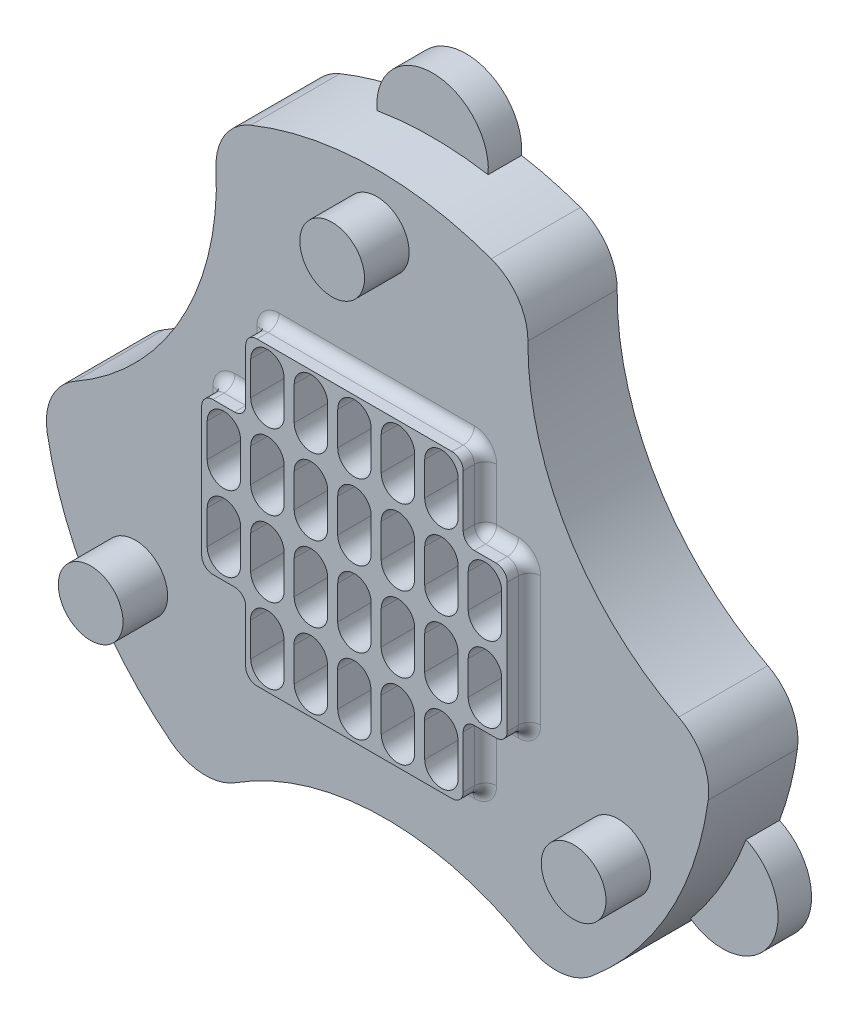
SolidWorks part; units mm, degrees
ref_plane "Спереди" through (0, 0, 0) normal (0, 0, 1) x (1, 0, 0)
ref_plane "Сверху" through (0, 0, 0) normal (0, 1, 0) x (1, 0, 0)
ref_plane "Справа" through (0, 0, 0) normal (1, 0, 0) x (0, 0, -1)
sketch "Sketch1" plane through (0, 0, 0) normal (0, 0, 1) x (1, 0, 0)
  line L0 (3.9, 6.755) -> (7.8, 0) construction
  line L2 (5.85, 10.1325) -> (11.7, 0) construction
  line L4 (7.8, 13.51) -> (15.6, 0) construction
  circle A61 centre (0, 0) radius 20
  circle A131 centre (0, 0) radius 1.25
  circle A484 centre (3.9, 0) radius 1.25
  circle A485 centre (7.8, 0) radius 1.25
  circle A486 centre (11.7, 0) radius 1.25
  circle A487 centre (15.6, 0) radius 1.25
  circle A488 centre (1.95, -3.3775) radius 1.25
  circle A489 centre (3.9, -6.755) radius 1.25
  circle A490 centre (5.85, -10.1325) radius 1.25
  circle A491 centre (7.8, -13.51) radius 1.25
  circle A492 centre (-1.95, -3.3775) radius 1.25
  circle A493 centre (-3.9, -6.755) radius 1.25
  circle A494 centre (-5.85, -10.1325) radius 1.25
  circle A495 centre (-7.8, -13.51) radius 1.25
  circle A496 centre (-3.9, 0) radius 1.25
  circle A497 centre (-7.8, 0) radius 1.25
  circle A498 centre (-11.7, 0) radius 1.25
  circle A499 centre (-15.6, 0) radius 1.25
  circle A500 centre (-1.95, 3.3775) radius 1.25
  circle A501 centre (-3.9, 6.755) radius 1.25
  circle A502 centre (-5.85, 10.1325) radius 1.25
  circle A503 centre (-7.8, 13.51) radius 1.25
  circle A504 centre (1.95, 3.3775) radius 1.25
  circle A505 centre (3.9, 6.755) radius 1.25
  circle A506 centre (5.85, 10.1325) radius 1.25
  circle A507 centre (7.8, 13.51) radius 1.25
  circle A508 centre (5.85, 3.3775) radius 1.25
  circle A509 centre (7.8, 6.755) radius 1.25
  circle A510 centre (9.75, 3.3775) radius 1.25
  circle A511 centre (11.7, 6.755) radius 1.25
  circle A512 centre (9.7491, 10.1341) radius 1.25
  circle A513 centre (13.6509, 3.3759) radius 1.25
  circle A514 centre (5.85, -3.3791) radius 1.25
  circle A515 centre (9.75, -3.3791) radius 1.25
  circle A516 centre (7.8, -6.7566) radius 1.25
  circle A517 centre (11.7, -6.7566) radius 1.25
  circle A518 centre (9.7491, -10.1356) radius 1.25
  circle A519 centre (13.6509, -3.3775) radius 1.25
  circle A520 centre (-0.0013, -6.7573) radius 1.25
  circle A521 centre (1.9487, -10.1348) radius 1.25
  circle A522 centre (-1.9513, -10.1348) radius 1.25
  circle A523 centre (-0.0013, -13.5123) radius 1.25
  circle A524 centre (-3.9032, -13.5123) radius 1.25
  circle A525 centre (3.9005, -13.5123) radius 1.25
  circle A526 centre (-5.8527, -3.3791) radius 1.25
  circle A527 centre (-7.8027, -6.7566) radius 1.25
  circle A528 centre (-9.7527, -3.3791) radius 1.25
  circle A529 centre (-11.7027, -6.7566) radius 1.25
  circle A530 centre (-13.6536, -3.3775) radius 1.25
  circle A531 centre (-9.7518, -10.1356) radius 1.25
  circle A532 centre (-5.8527, 3.3775) radius 1.25
  circle A533 centre (-9.7527, 3.3775) radius 1.25
  circle A534 centre (-7.8027, 6.755) radius 1.25
  circle A535 centre (-11.7027, 6.755) radius 1.25
  circle A536 centre (-9.7518, 10.1341) radius 1.25
  circle A537 centre (-13.6536, 3.3759) radius 1.25
  circle A538 centre (-0.0014, 6.7558) radius 1.25
  circle A539 centre (-1.9514, 10.1333) radius 1.25
  circle A540 centre (1.9486, 10.1333) radius 1.25
  circle A541 centre (-0.0014, 13.5108) radius 1.25
  circle A542 centre (3.9005, 13.5108) radius 1.25
  circle A543 centre (-3.9032, 13.5108) radius 1.25
  circle A544 centre (13.65, -1.1258) radius 2.2517 construction
  circle A545 centre (11.7009, -4.5044) radius 2.2522 construction
  circle A546 centre (9.75, -7.8834) radius 2.2522 construction
  circle A547 centre (7.7987, -11.2591) radius 2.2509 construction
  circle A548 centre (13.65, -1.1258) radius 0.65
  circle A549 centre (11.7009, -4.5044) radius 0.65
  circle A550 centre (9.75, -7.8834) radius 0.65
  circle A551 centre (7.7987, -11.2591) radius 0.65
  circle A552 centre (9.75, -1.1258) radius 0.65
  circle A553 centre (7.8009, -4.5044) radius 0.65
  circle A554 centre (5.85, -7.8834) radius 0.65
  circle A555 centre (3.8987, -11.2591) radius 0.65
  circle A556 centre (5.85, -1.1258) radius 0.65
  circle A557 centre (3.9009, -4.5044) radius 0.65
  circle A558 centre (1.95, -7.8834) radius 0.65
  circle A559 centre (-0.0013, -11.2591) radius 0.65
  circle A560 centre (1.95, -1.1258) radius 0.65
  circle A561 centre (0.0009, -4.5044) radius 0.65
  circle A562 centre (-1.95, -7.8834) radius 0.65
  circle A563 centre (-3.9013, -11.2591) radius 0.65
  circle A564 centre (-1.95, -1.1258) radius 0.65
  circle A565 centre (-3.8991, -4.5044) radius 0.65
  circle A566 centre (-5.85, -7.8834) radius 0.65
  circle A567 centre (-7.8013, -11.2591) radius 0.65
  circle A568 centre (-5.85, -1.1258) radius 0.65
  circle A569 centre (-7.7991, -4.5044) radius 0.65
  circle A570 centre (-9.75, -7.8834) radius 0.65
  circle A572 centre (-9.75, -1.1258) radius 0.65
  circle A573 centre (-11.6991, -4.5044) radius 0.65
  circle A576 centre (-13.65, -1.1258) radius 0.65
  circle A587 centre (0, 2.2517) radius 2.2517 construction
  circle A588 centre (0, 2.2517) radius 0.65
  circle A589 centre (3.9, 2.2517) radius 0.65
  circle A590 centre (7.8, 2.2517) radius 0.65
  circle A591 centre (11.7, 2.2517) radius 0.65
  circle A592 centre (15.6, 2.2517) radius 0.65
  circle A593 centre (1.9491, 5.6297) radius 2.2522 construction
  circle A594 centre (1.9491, 5.6297) radius 0.65
  circle A595 centre (5.8491, 5.6297) radius 0.65
  circle A596 centre (9.7491, 5.6297) radius 0.65
  circle A597 centre (13.6491, 5.6297) radius 0.65
  circle A598 centre (3.8991, 9.0072) radius 2.2522 construction
  circle A599 centre (3.8991, 9.0072) radius 0.65
  circle A600 centre (7.7991, 9.0072) radius 0.65
  circle A601 centre (11.6991, 9.0072) radius 0.65
  circle A602 centre (5.85, 12.3842) radius 2.2517 construction
  circle A603 centre (5.85, 12.3842) radius 0.65
  circle A604 centre (9.75, 12.3842) radius 0.65
  circle A605 centre (5.85, -14.6358) radius 0.65
  circle A606 centre (1.9509, -14.6353) radius 0.65
  circle A607 centre (-1.9491, -14.6353) radius 0.65
  circle A608 centre (-5.85, -14.6358) radius 0.65
  circle A609 centre (-15.6, 2.2517) radius 0.65
  circle A610 centre (-13.65, 5.6281) radius 0.65
  circle A611 centre (-11.7, 9.0056) radius 0.65
  circle A612 centre (-9.75, 12.3842) radius 0.65
  circle A613 centre (-5.85, 12.3842) radius 0.65
  circle A614 centre (-1.95, 12.3842) radius 0.65
  circle A615 centre (1.95, 12.3842) radius 0.65
  circle A616 centre (-7.8, 9.0056) radius 0.65
  circle A617 centre (-9.75, 5.6281) radius 0.65
  circle A618 centre (-11.7, 2.2517) radius 0.65
  circle A619 centre (-3.9, 9.0056) radius 0.65
  circle A620 centre (-5.85, 5.6281) radius 0.65
  circle A621 centre (-7.8, 2.2517) radius 0.65
  circle A622 centre (0, 9.0056) radius 0.65
  circle A623 centre (-1.95, 5.6281) radius 0.65
  circle A624 centre (-3.9, 2.2517) radius 0.65
  circle A625 centre (-15.5991, -4.5044) radius 0.65
  circle A626 centre (-13.65, -7.8834) radius 0.65
  circle A627 centre (-17.55, -7.8834) radius 0.65
  circle A628 centre (-19.5013, -11.2591) radius 0.65
  circle A629 centre (-15.6013, -11.2591) radius 0.65
  circle A630 centre (-11.7013, -11.2591) radius 0.65
  point P51 (0, 0)
  point P125 (-0.0013, -0.0008)
  point P231 (0, 0)
  dimension "D1" = 5
  dimension "D3" = 6
  dimension "D5" = 8
  dimension "D7" = 4
  dimension "D11" = 4
  dimension "D2" = 6
  dimension "D6" = 5
  dimension "D8" = 3
  dimension "D9" = 2
  dimension "D4" = 1.3
  dimension "D10" = 3
ref_plane "Plane1" through (0, 0, 10) normal (0, 0, 1) x (1, 0, 0)
sketch "Sketch2" plane through (0, 0, 10) normal (0, 0, 1) x (1, 0, 0)
  line L0 (-7.8, 13.51) -> (-7.8027, 6.755) construction
  line L1 (-9.7518, 10.1341) -> (-5.85, 10.1325) construction
  line L2 (-7.8008, 11.6325) -> (-7.8019, 8.6325) construction
  line L3 (-6.3008, 11.6319) -> (-6.3019, 8.6319)
  line L4 (-9.3008, 11.6331) -> (-9.3019, 8.6331)
  line L5 (-5.4008, 11.6331) -> (-5.4019, 8.6331)
  line L6 (-2.4008, 11.6319) -> (-2.4019, 8.6319)
  line L7 (-3.9008, 11.6325) -> (-3.9019, 8.6325) construction
  line L8 (-1.5008, 11.6331) -> (-1.5019, 8.6331)
  line L9 (1.4992, 11.6319) -> (1.4981, 8.6319)
  line L10 (-0.0008, 11.6325) -> (-0.0019, 8.6325) construction
  line L11 (2.3992, 11.6331) -> (2.3981, 8.6331)
  line L12 (5.3992, 11.6319) -> (5.3981, 8.6319)
  line L13 (3.8992, 11.6325) -> (3.8981, 8.6325) construction
  line L14 (6.2992, 11.6331) -> (6.2981, 8.6331)
  line L15 (9.2992, 11.6319) -> (9.2981, 8.6319)
  line L16 (7.7992, 11.6325) -> (7.7981, 8.6325) construction
  line L17 (-9.7518, 10.1341) -> (-9.7527, 3.3775) construction
  line L18 (-11.7027, 6.755) -> (-7.8027, 6.755) construction
  line L19 (-10.2035, 1.8767) -> (-10.202, 4.8767)
  line L22 (-9.7527, 3.3775) -> (-5.8527, 3.3775) construction
  line L25 (-7.8027, 6.755) -> (-7.8, 0) construction
  line L26 (-7.8035, 1.8775) -> (-7.8019, 4.8775) construction
  line L27 (-9.3035, 1.8782) -> (-9.3019, 4.8782)
  line L28 (-6.3035, 1.8767) -> (-6.3019, 4.8767)
  line L29 (-2.4035, 1.8767) -> (-2.4019, 4.8767)
  line L30 (-5.4035, 1.8782) -> (-5.4019, 4.8782)
  line L31 (-3.9035, 1.8775) -> (-3.9019, 4.8775) construction
  line L32 (1.4965, 1.8767) -> (1.4981, 4.8767)
  line L33 (-1.5035, 1.8782) -> (-1.5019, 4.8782)
  line L34 (-0.0035, 1.8775) -> (-0.0019, 4.8775) construction
  line L35 (5.3965, 1.8767) -> (5.3981, 4.8767)
  line L36 (2.3965, 1.8782) -> (2.3981, 4.8782)
  line L37 (3.8965, 1.8775) -> (3.8981, 4.8775) construction
  line L38 (9.2965, 1.8767) -> (9.2981, 4.8767)
  line L39 (6.2965, 1.8782) -> (6.2981, 4.8782)
  line L40 (7.7965, 1.8775) -> (7.7981, 4.8775) construction
  line L41 (13.1965, 1.8767) -> (13.1981, 4.8767)
  line L42 (10.1965, 1.8782) -> (10.1981, 4.8782)
  line L43 (11.6965, 1.8775) -> (11.6981, 4.8775) construction
  line L44 (-13.2035, 1.8782) -> (-13.2019, 4.8782)
  line L45 (-11.7035, 1.8775) -> (-11.702, 4.8775) construction
  line L46 (-9.7527, -3.3791) -> (-5.8527, -3.3791) construction
  line L47 (-7.8, 0) -> (-7.8027, -6.7566) construction
  line L48 (-7.8046, -4.8791) -> (-7.8008, -1.8791) construction
  line L49 (-9.3046, -4.8771) -> (-9.3007, -1.8771)
  line L50 (-6.3047, -4.881) -> (-6.3008, -1.881)
  line L51 (-2.4047, -4.881) -> (-2.4008, -1.881)
  line L52 (-5.4046, -4.8771) -> (-5.4007, -1.8771)
  line L53 (-3.9046, -4.8791) -> (-3.9008, -1.8791) construction
  line L54 (1.4953, -4.881) -> (1.4992, -1.881)
  line L55 (-1.5046, -4.8771) -> (-1.5007, -1.8771)
  line L56 (-0.0046, -4.8791) -> (-0.0008, -1.8791) construction
  line L57 (5.3953, -4.881) -> (5.3992, -1.881)
  line L58 (2.3954, -4.8771) -> (2.3993, -1.8771)
  line L59 (3.8954, -4.8791) -> (3.8992, -1.8791) construction
  line L60 (9.2953, -4.881) -> (9.2992, -1.881)
  line L61 (6.2954, -4.8771) -> (6.2993, -1.8771)
  line L62 (7.7954, -4.8791) -> (7.7992, -1.8791) construction
  line L63 (13.1953, -4.881) -> (13.1992, -1.881)
  line L64 (10.1954, -4.8771) -> (10.1993, -1.8771)
  line L65 (11.6954, -4.8791) -> (11.6992, -1.8791) construction
  line L66 (-10.2047, -4.881) -> (-10.2008, -1.881)
  line L67 (-13.2046, -4.8771) -> (-13.2007, -1.8771)
  line L68 (-11.7046, -4.8791) -> (-11.7008, -1.8791) construction
  line L69 (-9.7518, -10.1356) -> (-5.482, -10.1356) construction
  line L70 (-7.8027, -6.7566) -> (-7.8, -13.51) construction
  line L71 (-7.8259, -8.6356) -> (-7.8007, -11.6356) construction
  line L72 (-6.3259, -8.623) -> (-6.3008, -11.623)
  line L73 (-9.3258, -8.6482) -> (-9.3007, -11.6482)
  line L74 (-5.4258, -8.6482) -> (-5.4007, -11.6482)
  line L75 (-2.4259, -8.623) -> (-2.4008, -11.623)
  line L76 (-3.9259, -8.6356) -> (-3.9007, -11.6356) construction
  line L77 (-1.5258, -8.6482) -> (-1.5007, -11.6482)
  line L78 (1.4741, -8.623) -> (1.4992, -11.623)
  line L79 (-0.0259, -8.6356) -> (-0.0007, -11.6356) construction
  line L80 (2.3742, -8.6482) -> (2.3993, -11.6482)
  line L81 (5.3741, -8.623) -> (5.3992, -11.623)
  line L82 (3.8741, -8.6356) -> (3.8993, -11.6356) construction
  line L83 (6.2742, -8.6482) -> (6.2993, -11.6482)
  line L84 (9.2741, -8.623) -> (9.2992, -11.623)
  line L85 (7.7741, -8.6356) -> (7.7993, -11.6356) construction
  arc A0 (-6.3008, 11.6319) -> (-9.3008, 11.6331) centre (-7.8008, 11.6325) ccw
  arc A1 (-9.3019, 8.6331) -> (-6.3019, 8.6319) centre (-7.8019, 8.6325) ccw
  arc A2 (-2.4008, 11.6319) -> (-5.4008, 11.6331) centre (-3.9008, 11.6325) ccw
  arc A3 (-5.4019, 8.6331) -> (-2.4019, 8.6319) centre (-3.9019, 8.6325) ccw
  arc A4 (1.4992, 11.6319) -> (-1.5008, 11.6331) centre (-0.0008, 11.6325) ccw
  arc A5 (-1.5019, 8.6331) -> (1.4981, 8.6319) centre (-0.0019, 8.6325) ccw
  arc A6 (5.3992, 11.6319) -> (2.3992, 11.6331) centre (3.8992, 11.6325) ccw
  arc A7 (2.3981, 8.6331) -> (5.3981, 8.6319) centre (3.8981, 8.6325) ccw
  arc A8 (9.2992, 11.6319) -> (6.2992, 11.6331) centre (7.7992, 11.6325) ccw
  arc A9 (6.2981, 8.6331) -> (9.2981, 8.6319) centre (7.7981, 8.6325) ccw
  arc A14 (-9.3035, 1.8782) -> (-6.3035, 1.8767) centre (-7.8035, 1.8775) ccw
  arc A15 (-6.3019, 4.8767) -> (-9.3019, 4.8782) centre (-7.8019, 4.8775) ccw
  arc A16 (-5.4035, 1.8782) -> (-2.4035, 1.8767) centre (-3.9035, 1.8775) ccw
  arc A17 (-2.4019, 4.8767) -> (-5.4019, 4.8782) centre (-3.9019, 4.8775) ccw
  arc A18 (-1.5035, 1.8782) -> (1.4965, 1.8767) centre (-0.0035, 1.8775) ccw
  arc A19 (1.4981, 4.8767) -> (-1.5019, 4.8782) centre (-0.0019, 4.8775) ccw
  arc A20 (2.3965, 1.8782) -> (5.3965, 1.8767) centre (3.8965, 1.8775) ccw
  arc A21 (5.3981, 4.8767) -> (2.3981, 4.8782) centre (3.8981, 4.8775) ccw
  arc A22 (6.2965, 1.8782) -> (9.2965, 1.8767) centre (7.7965, 1.8775) ccw
  arc A23 (9.2981, 4.8767) -> (6.2981, 4.8782) centre (7.7981, 4.8775) ccw
  arc A24 (10.1965, 1.8782) -> (13.1965, 1.8767) centre (11.6965, 1.8775) ccw
  arc A25 (13.1981, 4.8767) -> (10.1981, 4.8782) centre (11.6981, 4.8775) ccw
  arc A26 (-13.2035, 1.8782) -> (-10.2035, 1.8767) centre (-11.7035, 1.8775) ccw
  arc A27 (-10.202, 4.8767) -> (-13.2019, 4.8782) centre (-11.702, 4.8775) ccw
  arc A28 (-9.3046, -4.8771) -> (-6.3047, -4.881) centre (-7.8046, -4.8791) ccw
  arc A29 (-6.3008, -1.881) -> (-9.3007, -1.8771) centre (-7.8008, -1.8791) ccw
  arc A30 (-5.4046, -4.8771) -> (-2.4047, -4.881) centre (-3.9046, -4.8791) ccw
  arc A31 (-2.4008, -1.881) -> (-5.4007, -1.8771) centre (-3.9008, -1.8791) ccw
  arc A32 (-1.5046, -4.8771) -> (1.4953, -4.881) centre (-0.0046, -4.8791) ccw
  arc A33 (1.4992, -1.881) -> (-1.5007, -1.8771) centre (-0.0008, -1.8791) ccw
  arc A34 (2.3954, -4.8771) -> (5.3953, -4.881) centre (3.8954, -4.8791) ccw
  arc A35 (5.3992, -1.881) -> (2.3993, -1.8771) centre (3.8992, -1.8791) ccw
  arc A36 (6.2954, -4.8771) -> (9.2953, -4.881) centre (7.7954, -4.8791) ccw
  arc A37 (9.2992, -1.881) -> (6.2993, -1.8771) centre (7.7992, -1.8791) ccw
  arc A38 (10.1954, -4.8771) -> (13.1953, -4.881) centre (11.6954, -4.8791) ccw
  arc A39 (13.1992, -1.881) -> (10.1993, -1.8771) centre (11.6992, -1.8791) ccw
  arc A40 (-13.2046, -4.8771) -> (-10.2047, -4.881) centre (-11.7046, -4.8791) ccw
  arc A41 (-10.2008, -1.881) -> (-13.2007, -1.8771) centre (-11.7008, -1.8791) ccw
  arc A42 (-6.3259, -8.623) -> (-9.3258, -8.6482) centre (-7.8259, -8.6356) ccw
  arc A43 (-9.3007, -11.6482) -> (-6.3008, -11.623) centre (-7.8007, -11.6356) ccw
  arc A44 (-2.4259, -8.623) -> (-5.4258, -8.6482) centre (-3.9259, -8.6356) ccw
  arc A45 (-5.4007, -11.6482) -> (-2.4008, -11.623) centre (-3.9007, -11.6356) ccw
  arc A46 (1.4741, -8.623) -> (-1.5258, -8.6482) centre (-0.0259, -8.6356) ccw
  arc A47 (-1.5007, -11.6482) -> (1.4992, -11.623) centre (-0.0007, -11.6356) ccw
  arc A48 (5.3741, -8.623) -> (2.3742, -8.6482) centre (3.8741, -8.6356) ccw
  arc A49 (2.3993, -11.6482) -> (5.3992, -11.623) centre (3.8993, -11.6356) ccw
  arc A50 (9.2741, -8.623) -> (6.2742, -8.6482) centre (7.7741, -8.6356) ccw
  arc A51 (6.2993, -11.6482) -> (9.2992, -11.623) centre (7.7993, -11.6356) ccw
  circle A52 centre (0, 0) radius 16.85 construction
  circle A53 centre (0, 0) radius 18.85
  point P10 (-7.8014, 10.1325)
  point P18 (-3.9014, 10.1325)
  point P25 (-0.0014, 10.1325)
  point P32 (3.8986, 10.1325)
  point P39 (7.7986, 10.1325)
  point P50 (-11.7027, 3.3775)
  point P58 (-7.8027, 3.3775)
  point P68 (-3.9027, 3.3775)
  point P75 (-0.0027, 3.3775)
  point P82 (3.8973, 3.3775)
  point P89 (7.7973, 3.3775)
  point P96 (11.6973, 3.3775)
  point P108 (-7.8027, -3.3791)
  point P116 (-3.9027, -3.3791)
  point P123 (-0.0027, -3.3791)
  point P130 (3.8973, -3.3791)
  point P137 (7.7973, -3.3791)
  point P144 (11.6973, -3.3791)
  point P151 (-11.7027, -3.3791)
  point P162 (-7.8133, -10.1356)
  point P170 (-3.9133, -10.1356)
  point P177 (-0.0133, -10.1356)
  point P184 (3.8867, -10.1356)
  point P191 (7.7867, -10.1356)
  dimension "D1" = 3
  dimension "D15" = 2
  dimension "D2" = 3
  dimension "D4" = 2
  dimension "D5" = 3
  dimension "D6" = 3
  dimension "D7" = 3
  dimension "D9" = 3
  dimension "D12" = 3
  dimension "D13" = 3
  dimension "D3" = 5
  dimension "D8" = 6
  dimension "D10" = 6
  dimension "D11" = 2
  dimension "D14" = 5
extrude "Boss-Extrude1" add sketch "Sketch2" along normal blind 8
sketch "Sketch3" plane through (0, 0, 18) normal (0, 0, 1) x (1, 0, 0)
  circle A0 centre (0, 0) radius 17.6
  circle A1 centre (0, 0) radius 30
extrude "Boss-Extrude2" add sketch "Sketch3" against normal up to surface (8 mm away) up to face at (3.8867, -10.1356, 10)
sketch "Sketch4" plane through (0, 0, 18) normal (0, 0, 1) x (1, 0, 0)
  circle A0 centre (0, 0) radius 25 construction
  circle A1 centre (0, 25) radius 2.9
  circle A2 centre (21.6506, -12.5) radius 2.9
  circle A3 centre (-21.6506, -12.5) radius 2.9
  point P11 (0, 0)
  dimension "D1" = 3
extrude "Boss-Extrude3" add sketch "Sketch4" along normal blind 4
sketch "Sketch6" plane through (0, 0, 10) normal (0, 0, -1) x (-1, 0, 0)
  circle A0 centre (0, 30) radius 5
  circle A1 centre (0, 0) radius 30 construction
  circle A2 centre (25.9808, -15) radius 5
  circle A3 centre (-25.9808, -15) radius 5
  point P10 (0, 0)
  dimension "D1" = 3
extrude "Boss-Extrude4" add sketch "Sketch6" against normal blind 3
sketch "Sketch5" plane through (0, 0, 10) normal (0, 0, -1) x (-1, 0, 0)
  circle A0 centre (0, 25) radius 3
  circle A1 centre (21.6506, -12.5) radius 3
  circle A2 centre (-21.6506, -12.5) radius 3
extrude "Cut-Extrude1" cut sketch "Sketch5" against normal blind 3
sketch "Sketch7" plane through (0, 0, 10) normal (0, 0, -1) x (-1, 0, 0)
  line L0 (0, 0) -> (-38.5501, 23.214) construction
  circle A0 centre (0, 0) radius 45 construction
  circle A1 centre (-38.5501, 23.214) radius 25
  circle A2 centre (39.379, 21.7783) radius 25
  circle A3 centre (-0.8289, -44.9924) radius 25
  circle A4 centre (0, 0) radius 19 construction
  point P11 (0, 0)
  dimension "D1" = 3
extrude "Cut-Extrude2" cut sketch "Sketch7" against normal blind 8
fillet "Fillet1" radius 5 6 edges at (-14.7586, 26.1186, 14) (-29.9681, -1.3827, 14) (-15.2401, -25.8407, 14) (16.1815, -25.2618, 14) (29.9987, -0.278, 14) (13.7866, 26.6445, 14)
extrude "Boss-Extrude5" add sketch "Sketch2<2>" along normal blind 10
sketch "Sketch2<2>" plane through (0, 0, 10) normal (0, 0, 1) x (1, 0, 0) same geometry as "Sketch2"
sketch "Sketch8" plane through (0, 0, 20) normal (0, 0, 1) x (1, 0, 0)
  line L0 (0, 0) -> (6.0128, 0) construction
  line L1 (-9.7495, -6.7926) -> (9.7495, -6.7926)
  line L2 (0, 0) -> (0, 5.1095) construction
  line L3 (-9.7495, 13.4736) -> (9.7495, 13.4736)
  line L4 (-9.7495, 13.4736) -> (-9.7495, 6.7926)
  line L5 (-9.7495, 6.7926) -> (9.7495, 6.7926)
  line L6 (9.7495, 13.4736) -> (9.7495, 6.7926)
  line L7 (-9.7495, 13.4736) -> (9.7495, 6.7926) construction
  line L8 (-9.7495, 6.7926) -> (9.7495, 13.4736) construction
  line L9 (-13.6953, -6.7926) -> (13.6953, -6.7926)
  line L10 (-13.6953, -6.7926) -> (-13.6953, 6.7926)
  line L11 (-13.6953, 6.7926) -> (13.6953, 6.7926)
  line L12 (13.6953, -6.7926) -> (13.6953, 6.7926)
  line L13 (-13.6953, -6.7926) -> (13.6953, 6.7926) construction
  line L14 (-13.6953, 6.7926) -> (13.6953, -6.7926) construction
  line L15 (9.7495, -13.4736) -> (9.7495, -6.7926)
  line L16 (-9.7495, -13.4736) -> (9.7495, -13.4736)
  line L17 (-9.7495, -13.4736) -> (-9.7495, -6.7926)
  circle A0 centre (0, 0) radius 20.5111
  point P3 (0, 10.1331)
extrude "Cut-Extrude3" cut sketch "Sketch8" against normal blind 2 contours A0 L16 L17 L9 L10 L11 L4 L3 L6 L12 L15 region at (-19.9309, 0, 20)
fillet "Fillet2" radius 1 12 edges at (9.7495, 13.4736, 19) (9.7495, 6.7926, 19) (13.6953, 6.7926, 19) (13.6953, -6.7926, 19) (9.7495, -6.7926, 19) (9.7495, -13.4736, 19) (-9.7495, -13.4736, 19) (-9.7495, -6.7926, 19) (-13.6953, -6.7926, 19) (-13.6953, 6.7926, 19) (-9.7495, 6.7926, 19) (-9.7495, 13.4736, 19)
fillet "Fillet3" radius 1 24 edges at (-9.4566, 13.1807, 18) (0, 13.4736, 18) (9.4566, 13.1807, 18) (9.7495, 10.1331, 18) (10.0424, 7.0855, 18) (11.7224, 6.7926, 18) (13.4024, 6.4997, 18) (13.6953, 0, 18) (13.4024, -6.4997, 18) (11.7224, -6.7926, 18) (10.0424, -7.0855, 18) (9.7495, -10.1331, 18) (9.4566, -13.1807, 18) (0, -13.4736, 18) (-9.4566, -13.1807, 18) (-9.7495, -10.1331, 18) (-10.0424, -7.0855, 18) (-11.7224, -6.7926, 18) (-13.4024, -6.4997, 18) (-13.6953, 0, 18) (-13.4024, 6.4997, 18) (-11.7224, 6.7926, 18) (-10.0424, 7.0855, 18) (-9.7495, 10.1331, 18)
sketch "Sketch9" plane through (0, 0, 10) normal (0, 0, 1) x (1, 0, 0)
  line L0 (5.85, 5.0278) -> (5.85, 8.4822) construction
  line L1 (4.9824, 5.0278) -> (4.9824, 8.4822)
  line L2 (6.7176, 5.0278) -> (6.7176, 8.4822)
  arc A0 (4.9824, 5.0278) -> (6.7176, 5.0278) centre (5.85, 5.0278) ccw
  arc A1 (6.7176, 8.4822) -> (4.9824, 8.4822) centre (5.85, 8.4822) ccw
  point P2 (5.85, 6.755)
